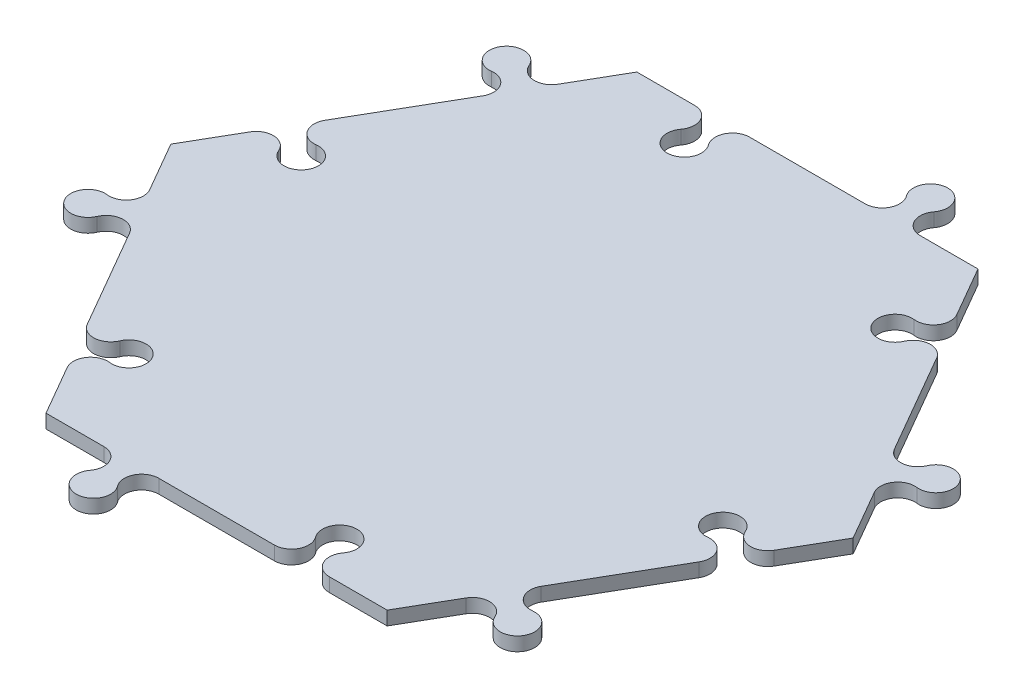
SolidWorks part; units mm, degrees
note: The reader was unsure of these and kept them because the rebuilt part matched: shared geometry of "Sketch2<3>".
ref_plane "Front Plane" through (0, 0, 0) normal (0, 0, 1) x (1, 0, 0)
ref_plane "Top Plane" through (0, 0, 0) normal (0, 1, 0) x (1, 0, 0)
ref_plane "Right Plane" through (0, 0, 0) normal (1, 0, 0) x (0, 0, -1)
sketch "Sketch1" plane through (0, 0, 0) normal (0, 1, 0) x (1, 0, 0)
  line L1 (-39.3753, 68.2) -> (-78.7506, 0)
  line L2 (-78.7506, 0) -> (-39.3753, -68.2)
  line L3 (-39.3753, -68.2) -> (39.3753, -68.2)
  line L7 (39.3753, -68.2) -> (78.7506, 0)
  line L8 (78.7506, 0) -> (39.3753, 68.2)
  line L9 (39.3753, 68.2) -> (-39.3753, 68.2)
  circle A0 centre (0, 0) radius 55.5 construction
  circle A1 centre (0, 0) radius 68.2 construction
  circle A2 centre (0, 0) radius 68.2 construction
  dimension "D1" = 111
  dimension "D2" = 12.7
extrude "Boss-Extrude1" add sketch "Sketch1" along normal blind 3.175
sketch "Sketch2" plane through (0, 0, 0) normal (0, 1, 0) x (1, 0, 0)
  line L0 (-13.3376, 68.2) -> (-26.0376, 68.2)
  line L1 (0, 0) -> (0, 68.2) construction
  line L2 (0, 0) -> (-39.3753, 68.2) construction
  line L3 (39.3753, 68.2) -> (-39.3753, 68.2) construction
  line L4 (19.6876, 68.2) -> (19.6876, 51.8907) construction
  line L5 (13.3376, 68.2) -> (26.0376, 68.2)
  arc A0 (-22.8626, 74.55) -> (-19.6876, 80.9) centre (-19.6876, 76.9313) cw construction
  arc A1 (-16.5126, 74.55) -> (-19.6876, 80.9) centre (-19.6876, 76.9313) ccw construction
  arc A2 (-13.3376, 68.2) -> (-16.5126, 74.55) centre (-13.3376, 72.1688) cw construction
  arc A3 (13.3376, 68.2) -> (16.5126, 74.55) centre (13.3376, 72.1688) ccw
  arc A4 (-26.0376, 68.2) -> (-22.8626, 74.55) centre (-26.0376, 72.1688) ccw construction
  arc A5 (16.5126, 74.55) -> (19.6876, 80.9) centre (19.6876, 76.9313) cw
  circle A6 centre (0, 0) radius 55.5 construction
  arc A7 (26.0376, 68.2) -> (22.8626, 74.55) centre (26.0376, 72.1688) cw
  arc A8 (22.8626, 74.55) -> (19.6876, 80.9) centre (19.6876, 76.9313) ccw
  arc A9 (-13.3376, 68.2) -> (-16.5126, 61.85) centre (-13.3376, 64.2313) ccw
  arc A10 (-16.5126, 61.85) -> (-19.6876, 55.5) centre (-19.6876, 59.4688) cw
  arc A11 (-22.8626, 61.85) -> (-19.6876, 55.5) centre (-19.6876, 59.4688) ccw
  arc A12 (-26.0376, 68.2) -> (-22.8626, 61.85) centre (-26.0376, 64.2313) cw
  circle A13 centre (-19.6876, 34.1) radius 1.5 construction
  dimension "D1" = 3
  dimension "D3" = 12.7
  dimension "D4" = 12.7
extrude "Boss-Extrude2" add sketch "Sketch2" along normal up to surface (3.175 mm away) contours A7 A8 A5 A3 L5 up to face at (0, 3.175, 0)
extrude "Cut-Extrude2" cut sketch "Sketch2<3>" along normal through all
sketch "Sketch2<3>" plane through (0, 0, 0) normal (0, 1, 0) x (1, 0, 0) same geometry as "Sketch2"
sketch "Sketch3" plane through (0, 0, 0) normal (0, 0, 1) x (1, 0, 0)
  line L0 (0, 0) -> (0, 25.4) construction
  dimension "D1" = 25.4
pattern_circular "CirPattern1" count 6 over 360 about axis through (0, 0, 0) along (0, 1, 0) of "Boss-Extrude2", "Cut-Extrude2"
